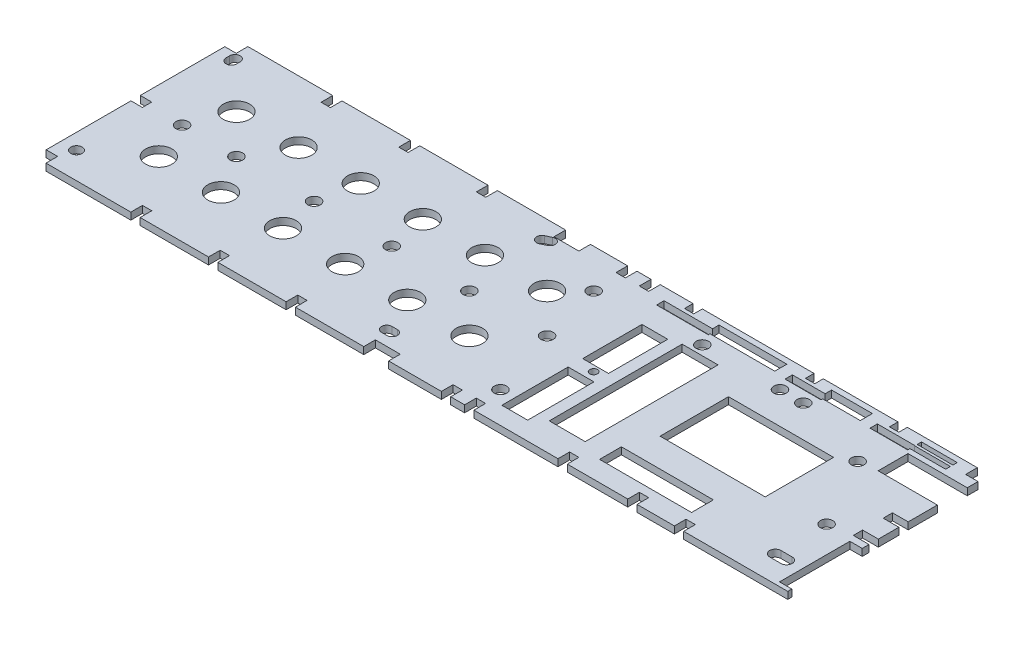
SolidWorks part; units mm, degrees
ref_plane "Front Plane" through (0, 0, 0) normal (0, 0, 1) x (1, 0, 0)
ref_plane "Top Plane" through (0, 0, 0) normal (0, 1, 0) x (1, 0, 0)
ref_plane "Right Plane" through (0, 0, 0) normal (1, 0, 0) x (0, 0, -1)
sketch "Sketch1" plane through (0, 0, 0) normal (0, 1, 0) x (1, 0, 0)
  line L0 (485, 0) -> (485, 130) construction
  line L1 (0, 130) -> (485, 130)
  line L2 (0, 130) -> (0, 0)
  line L3 (0, 0) -> (485, 0)
  line L4 (485, 130) -> (485, 0)
  line L5 (0, 130) -> (0, 0) construction
  line L6 (485, 130) -> (0, 130) construction
  line L7 (0, 0) -> (485, 0) construction
  line L8 (444.7316, 118.9355) -> (444.7316, 117.5)
  line L9 (485, 47.9413) -> (477.0415, 47.9413)
  line L10 (485, 47.9413) -> (485, 2.6445)
  line L11 (485, 2.6445) -> (477.0415, 2.6445)
  line L12 (477.0415, 47.9413) -> (477.0415, 2.6445)
  line L13 (485, 77.533) -> (474.8926, 77.533)
  line L14 (485, 77.533) -> (485, 71.533)
  line L15 (485, 71.533) -> (474.8926, 71.533)
  line L16 (474.8926, 77.533) -> (474.8926, 71.533)
  line L17 (485, 58.3069) -> (474.8926, 58.3069)
  line L18 (485, 58.3069) -> (485, 52.3069)
  line L19 (485, 52.3069) -> (474.8926, 52.3069)
  line L20 (474.8926, 58.3069) -> (474.8926, 52.3069)
  line L21 (485, 115.574) -> (446.8521, 115.574)
  line L22 (485, 115.574) -> (485, 96.3378)
  line L23 (485, 96.3378) -> (446.8521, 96.3378)
  line L24 (446.8521, 115.574) -> (446.8521, 96.3378)
  line L25 (444.7316, 126.4) -> (467.7258, 126.4)
  line L26 (444.7316, 126.4) -> (444.7316, 123.5923)
  line L27 (444.7316, 123.5923) -> (467.7258, 123.5923)
  line L28 (467.7258, 126.4) -> (467.7258, 123.5923)
  line L29 (467.6918, 122.0219) -> (444.7316, 122.0219)
  line L30 (467.6918, 122.0219) -> (467.6918, 118.9355)
  line L31 (467.6918, 118.9355) -> (444.7316, 118.9355)
  line L33 (425.9983, 130) -> (431.9983, 130)
  line L34 (425.9983, 130) -> (425.9983, 124.5)
  line L35 (425.9983, 124.5) -> (431.9983, 124.5)
  line L36 (431.9983, 130) -> (431.9983, 124.5)
  line L37 (420.448, 122.2354) -> (444.7316, 122.2354)
  line L38 (420.448, 122.2354) -> (420.448, 117.5)
  line L39 (420.448, 117.5) -> (444.7316, 117.5)
  line L40 (444.7316, 122.2354) -> (444.7316, 122.0219)
  line L41 (10.0347, 119.0046) -> (10.0347, 116.6922) construction
  line L42 (371.8879, 130) -> (377.8879, 130)
  line L43 (371.8879, 130) -> (371.8879, 124.5)
  line L44 (371.8879, 124.5) -> (377.8879, 124.5)
  line L45 (377.8879, 130) -> (377.8879, 124.5)
  line L46 (294.0008, 130) -> (300.0008, 130)
  line L47 (294.0008, 130) -> (294.0008, 124.5)
  line L48 (294.0008, 124.5) -> (300.0008, 124.5)
  line L49 (300.0008, 130) -> (300.0008, 124.5)
  line L50 (266.9165, 130) -> (272.9165, 130)
  line L51 (266.9165, 130) -> (266.9165, 122.5)
  line L52 (266.9165, 122.5) -> (272.9165, 122.5)
  line L53 (272.9165, 130) -> (272.9165, 122.5)
  line L54 (251.9112, 130) -> (257.9112, 130)
  line L55 (251.9112, 130) -> (251.9112, 122.5)
  line L56 (251.9112, 122.5) -> (257.9112, 122.5)
  line L57 (257.9112, 130) -> (257.9112, 122.5)
  line L58 (211.9807, 130) -> (227.9807, 130)
  line L59 (211.9807, 130) -> (211.9807, 122.5)
  line L60 (211.9807, 122.5) -> (227.9807, 122.5)
  line L61 (227.9807, 130) -> (227.9807, 122.5)
  line L62 (161.992, 130) -> (167.992, 130)
  line L63 (161.992, 130) -> (161.992, 122.5)
  line L64 (161.992, 122.5) -> (167.992, 122.5)
  line L65 (167.992, 130) -> (167.992, 122.5)
  line L66 (112.0325, 130) -> (118.0325, 130)
  line L67 (112.0325, 130) -> (112.0325, 122.5)
  line L68 (112.0325, 122.5) -> (118.0325, 122.5)
  line L69 (118.0325, 130) -> (118.0325, 122.5)
  line L70 (62.0027, 130) -> (68.0027, 130)
  line L71 (62.0027, 130) -> (62.0027, 122.5)
  line L72 (62.0027, 122.5) -> (68.0027, 122.5)
  line L73 (68.0027, 130) -> (68.0027, 122.5)
  line L74 (425.0315, 89.4923) -> (357.3425, 89.4923)
  line L75 (425.0315, 89.4923) -> (425.0315, 45.4306)
  line L76 (425.0315, 45.4306) -> (357.3425, 45.4306)
  line L77 (357.3425, 89.4923) -> (357.3425, 45.4306)
  line L78 (410.025, 27.0715) -> (350.7971, 27.0715)
  line L79 (410.025, 27.0715) -> (410.025, 13.0229)
  line L80 (410.025, 13.0229) -> (350.7971, 13.0229)
  line L81 (350.7971, 27.0715) -> (350.7971, 13.0229)
  line L82 (289.1745, 101.9445) -> (305.7775, 101.9445)
  line L83 (289.1745, 101.9445) -> (289.1745, 63.8011)
  line L84 (289.1745, 11.7457) -> (305.7775, 11.7457)
  line L85 (305.7775, 101.9445) -> (305.7775, 63.8011)
  line L86 (313.1211, 103.8603) -> (336.2695, 103.8603)
  line L87 (313.1211, 103.8603) -> (313.1211, 18.2911)
  line L88 (313.1211, 18.2911) -> (336.2695, 18.2911)
  line L89 (336.2695, 103.8603) -> (336.2695, 18.2911)
  line L90 (411.997, 0) -> (417.997, 0)
  line L91 (411.997, 0) -> (411.997, 7.5)
  line L92 (411.997, 7.5) -> (417.997, 7.5)
  line L93 (417.997, 0) -> (417.997, 7.5)
  line L94 (381.9632, 0) -> (387.9632, 0)
  line L95 (381.9632, 0) -> (381.9632, 7.5)
  line L96 (381.9632, 7.5) -> (387.9632, 7.5)
  line L97 (387.9632, 0) -> (387.9632, 7.5)
  line L98 (337.0209, 0) -> (343.0209, 0)
  line L99 (337.0209, 0) -> (337.0209, 7.5)
  line L100 (337.0209, 7.5) -> (343.0209, 7.5)
  line L101 (343.0209, 0) -> (343.0209, 7.5)
  line L102 (261.9696, 0) -> (267.9696, 0)
  line L103 (261.9696, 0) -> (261.9696, 7.5)
  line L104 (261.9696, 7.5) -> (267.9696, 7.5)
  line L105 (267.9696, 0) -> (267.9696, 7.5)
  line L106 (276.9208, 0) -> (282.9208, 0)
  line L107 (276.9208, 0) -> (276.9208, 7.5)
  line L108 (276.9208, 7.5) -> (282.9208, 7.5)
  line L109 (282.9208, 0) -> (282.9208, 7.5)
  line L110 (211.9807, 0) -> (227.9807, 0)
  line L111 (211.9807, 0) -> (211.9807, 7.5)
  line L112 (211.9807, 7.5) -> (227.9807, 7.5)
  line L113 (227.9807, 0) -> (227.9807, 7.5)
  line L114 (161.992, 0) -> (167.992, 0)
  line L115 (161.992, 0) -> (161.992, 7.5)
  line L116 (161.992, 7.5) -> (167.992, 7.5)
  line L117 (167.992, 0) -> (167.992, 7.5)
  line L118 (112.0325, 0) -> (118.0325, 0)
  line L119 (112.0325, 0) -> (112.0325, 7.5)
  line L120 (112.0325, 7.5) -> (118.0325, 7.5)
  line L121 (118.0325, 0) -> (118.0325, 7.5)
  line L122 (62.0027, 0) -> (68.0027, 0)
  line L123 (62.0027, 0) -> (62.0027, 7.5)
  line L124 (62.0027, 7.5) -> (68.0027, 7.5)
  line L125 (68.0027, 0) -> (68.0027, 7.5)
  line L126 (0, 130) -> (7.3855, 130)
  line L127 (0, 130) -> (0, 122.5)
  line L128 (0, 122.5) -> (7.3855, 122.5)
  line L129 (7.3855, 130) -> (7.3855, 122.5)
  line L130 (0, 0) -> (7.3855, 0)
  line L131 (0, 0) -> (0, 7.5)
  line L132 (0, 7.5) -> (7.3855, 7.5)
  line L133 (7.3855, 0) -> (7.3855, 7.5)
  line L134 (485, 130) -> (477.0415, 130)
  line L135 (485, 130) -> (485, 122.492)
  line L136 (485, 122.492) -> (477.0415, 122.492)
  line L137 (477.0415, 130) -> (477.0415, 122.492)
  line L138 (0, 68.0866) -> (7.3855, 68.0866)
  line L139 (0, 68.0866) -> (0, 62.0866)
  line L140 (0, 62.0866) -> (7.3855, 62.0866)
  line L141 (7.3855, 68.0866) -> (7.3855, 62.0866)
  line L142 (13.4263, 119.0046) -> (13.4263, 116.6922)
  line L143 (6.6431, 119.0046) -> (6.6431, 116.6922)
  line L144 (209.8069, 16.987) -> (213.2636, 16.987) construction
  line L145 (209.8069, 20.3348) -> (213.2636, 20.3348)
  line L146 (209.8069, 13.6392) -> (213.2636, 13.6392)
  line L147 (213.2636, 118.5927) -> (209.7734, 116.9365) construction
  line L148 (214.7266, 115.5098) -> (211.2364, 113.8536)
  line L149 (211.8006, 121.6756) -> (208.3104, 120.0194)
  line L150 (460, 16.987) -> (467.2539, 16.987) construction
  line L151 (460, 20.6206) -> (467.2539, 20.6206)
  line L152 (460, 13.3534) -> (467.2539, 13.3534)
  line L153 (289.1745, 54.4287) -> (289.1745, 11.7457)
  line L154 (283.0858, 122.2354) -> (314.3348, 122.2354)
  line L155 (283.0858, 122.2354) -> (283.0858, 117.5)
  line L156 (283.0858, 117.5) -> (316.3348, 117.5)
  line L157 (316.3348, 118.5927) -> (316.3348, 117.5)
  line L158 (365.7301, 122.2354) -> (386.8323, 122.2354)
  line L159 (365.7301, 122.2354) -> (365.7301, 117.5)
  line L160 (365.7301, 117.5) -> (388.8323, 117.5)
  line L161 (388.8323, 118.5927) -> (388.8323, 117.5)
  line L162 (358.0245, 126.4) -> (314.3348, 126.4)
  line L163 (358.0245, 126.4) -> (358.0245, 118.5927)
  line L164 (358.0245, 118.5927) -> (316.3348, 118.5927)
  line L165 (314.3348, 126.4) -> (314.3348, 122.2354)
  line L166 (413.0962, 126.4) -> (386.8323, 126.4)
  line L167 (413.0962, 126.4) -> (413.0962, 118.5927)
  line L168 (413.0962, 118.5927) -> (388.8323, 118.5927)
  line L169 (386.8323, 126.4) -> (386.8323, 122.2354)
  line L170 (305.7775, 63.8011) -> (289.1745, 63.8011)
  line L172 (305.7775, 54.4287) -> (289.1745, 54.4287)
  line L174 (305.7775, 54.4287) -> (305.7775, 11.7457)
  circle A0 centre (40.0138, 90.005) radius 8.5
  circle A1 centre (65, 65) radius 4
  circle A2 centre (80.0138, 90.005) radius 8.5
  circle A3 centre (120.0138, 90.005) radius 8.5
  circle A4 centre (160.0138, 90.005) radius 8.5
  circle A5 centre (200.0138, 90.005) radius 8.5
  circle A6 centre (240.0138, 90.005) radius 8.5
  circle A7 centre (80.0138, 40.005) radius 8.5
  circle A8 centre (120.0138, 40.005) radius 8.5
  circle A9 centre (160.0138, 40.005) radius 8.5
  circle A10 centre (200.0138, 40.005) radius 8.5
  circle A11 centre (240.0138, 40.005) radius 8.5
  circle A12 centre (40.0138, 40.005) radius 8.5
  circle A13 centre (30, 65) radius 4
  circle A14 centre (115, 65) radius 4
  circle A15 centre (165, 65) radius 4
  circle A16 centre (215, 65) radius 4
  circle A17 centre (265, 65) radius 4
  circle A18 centre (255, 105) radius 4
  circle A19 centre (280, 20) radius 4
  circle A20 centre (320, 110) radius 4
  circle A21 centre (460, 50) radius 4
  circle A22 centre (435, 95) radius 4
  circle A23 centre (370, 110) radius 4
  circle A24 centre (385, 110) radius 4
  arc A25 (13.4263, 119.0046) -> (6.6431, 119.0046) centre (10.0347, 119.0046) ccw
  arc A26 (6.6431, 116.6922) -> (13.4263, 116.6922) centre (10.0347, 116.6922) ccw
  circle A27 centre (10.0347, 16.987) radius 3.6258
  arc A28 (209.8069, 20.3348) -> (209.8069, 13.6392) centre (209.8069, 16.987) ccw
  arc A29 (213.2636, 13.6392) -> (213.2636, 20.3348) centre (213.2636, 16.987) ccw
  arc A30 (214.7266, 115.5098) -> (211.8006, 121.6756) centre (213.2636, 118.5927) ccw
  arc A31 (208.3104, 120.0194) -> (211.2364, 113.8536) centre (209.7734, 116.9365) ccw
  arc A32 (460, 20.6206) -> (460, 13.3534) centre (460, 16.987) ccw
  arc A33 (467.2539, 13.3534) -> (467.2539, 20.6206) centre (467.2539, 16.987) ccw
  circle A34 centre (300, 60) radius 2.467
  point P202 (10.0347, 117.8484)
  point P207 (211.5352, 16.987)
  point P216 (211.5185, 117.7646)
  point P223 (463.6269, 16.987)
  dimension "D23" = 17
  dimension "D24" = 8
  dimension "D1" = 6
  dimension "D2" = 6
  dimension "D3" = 6
  dimension "D4" = 6
  dimension "D5" = 6
  dimension "D6" = 16
  dimension "D7" = 6
  dimension "D8" = 6
  dimension "D9" = 6
  dimension "D10" = 7.5
  dimension "D11" = 5.5
  dimension "D12" = 6
  dimension "D13" = 6
  dimension "D14" = 6
  dimension "D15" = 6
  dimension "D16" = 6
  dimension "D17" = 6
  dimension "D18" = 6
  dimension "D19" = 7.5
  dimension "D22" = 6
  dimension "D26" = 12.5
  dimension "D27" = 3.6
  dimension "D28" = 74.9387
  dimension "D29" = 47.3661
  dimension "D30" = 47.2438
  dimension "D20" = 6
  dimension "D21" = 2
  dimension "D25" = 5
extrude "Boss-Extrude1" add sketch "Sketch1" against normal blind 4.5 contours L138 L141 L140 L2 L132 L133 L3 L123 L124 L125 L119 L120 L121 L115 L116 L117 L111 L112 L113 L103 L104 L105 L107 L108 L109 L99 L100 L101 L95 L96 L97 L91 L92 L93 L4 L11 L12 L9 L19 L20 L17 region at (223.8274, 0, -64.3553)
